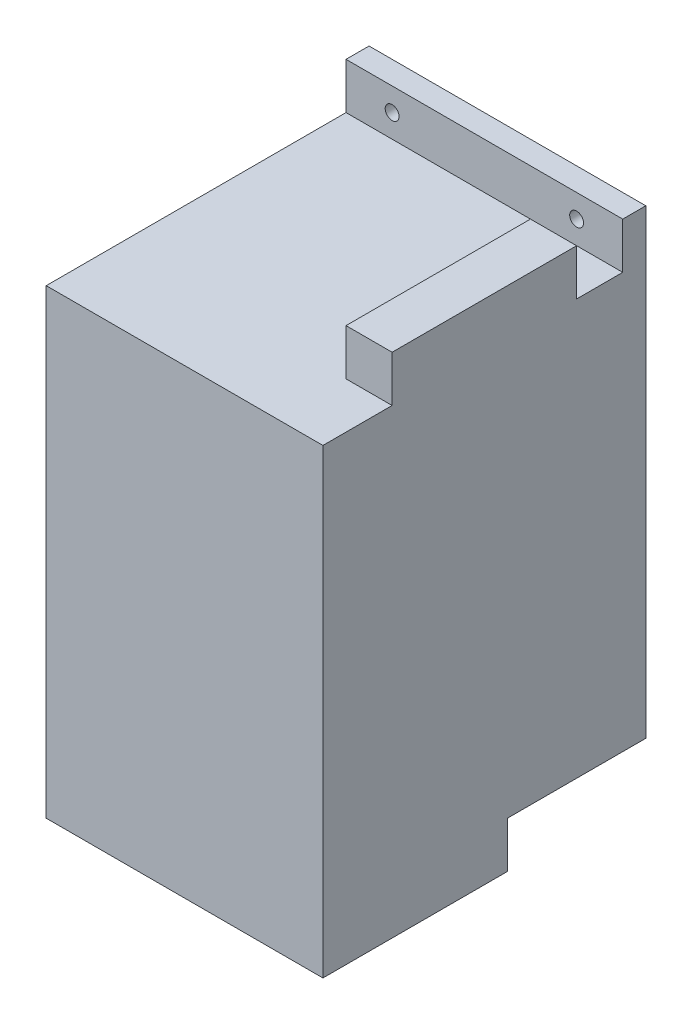
SolidWorks part; units mm, degrees
ref_plane "Front Plane" through (0, 0, 0) normal (0, 0, 1) x (1, 0, 0)
ref_plane "Top Plane" through (0, 0, 0) normal (0, 1, 0) x (1, 0, 0)
ref_plane "Right Plane" through (0, 0, 0) normal (1, 0, 0) x (0, 0, -1)
sketch "Sketch1" plane through (0, 0, 0) normal (0, 1, 0) x (1, 0, 0)
  line L1 (0, 0) -> (60, 0)
  line L2 (0, 0) -> (0, 70)
  line L3 (0, 70) -> (60, 70)
  line L4 (60, 0) -> (60, 70)
  dimension "D1" = 70
  dimension "D2" = 60
extrude "Boss-Extrude1" add sketch "Sketch1" along normal blind 100
sketch "Sketch2" plane through (0, 100, 0) normal (0, 1, 0) x (1, 0, 0)
  line L1 (50, 15) -> (60, 15)
  line L2 (50, 15) -> (50, 55)
  line L3 (50, 55) -> (60, 55)
  line L4 (60, 15) -> (60, 55)
  line L6 (60, 0) -> (60, 70) construction
  line L7 (60, 70) -> (0, 70) construction
  point P4 (0, 0)
  point P5 (0, 0)
  point P6 (60, 62.5893)
  point P8 (10, 0)
  point P9 (10, 52.3159)
  point P11 (60, 26.4245)
  point P12 (60, 51.8418)
  dimension "D1" = 10
  dimension "D2" = 15
  dimension "D3" = 40
extrude "Boss-Extrude2" add sketch "Sketch2" along normal blind 10
sketch "Sketch5" plane through (0, 100, 0) normal (0, 1, 0) x (1, 0, 0)
  line L0 (0, 70) -> (0, 0) construction
  line L1 (60, 70) -> (0, 70)
  line L2 (60, 70) -> (60, 65)
  line L3 (60, 65) -> (0, 65)
  line L4 (0, 70) -> (0, 65)
  dimension "D1" = 5
extrude "Boss-Extrude4" add sketch "Sketch5" along normal blind 10
sketch "Sketch6" plane through (0, 0, -70) normal (0, 0, -1) x (-1, 0, 0)
  line L0 (-60, 110) -> (-60, 0) construction
  line L1 (-60, 110) -> (0, 110) construction
  circle A0 centre (-50, 105) radius 1.5
  circle A1 centre (-10, 105) radius 1.5
  point P8 (0, 0)
  point P9 (0, 0)
  dimension "D1" = 40
  dimension "D4" = 3
  dimension "D5" = 3
  dimension "D2" = 10
  dimension "D3" = 5
extrude "Cut-Extrude4" cut sketch "Sketch6" against normal blind 10
sketch "Sketch7" plane through (0, 0, 0) normal (0, -1, 0) x (1, 0, 0)
  line L0 (60, -70) -> (0, -70) construction
  line L1 (60, -70) -> (0, -70)
  line L2 (60, -70) -> (60, -40)
  line L3 (60, -40) -> (0, -40)
  line L4 (0, -70) -> (0, -40)
  line L5 (0, -70) -> (0, 0) construction
  dimension "D1" = 30
extrude "Cut-Extrude5" cut sketch "Sketch7" against normal blind 10
